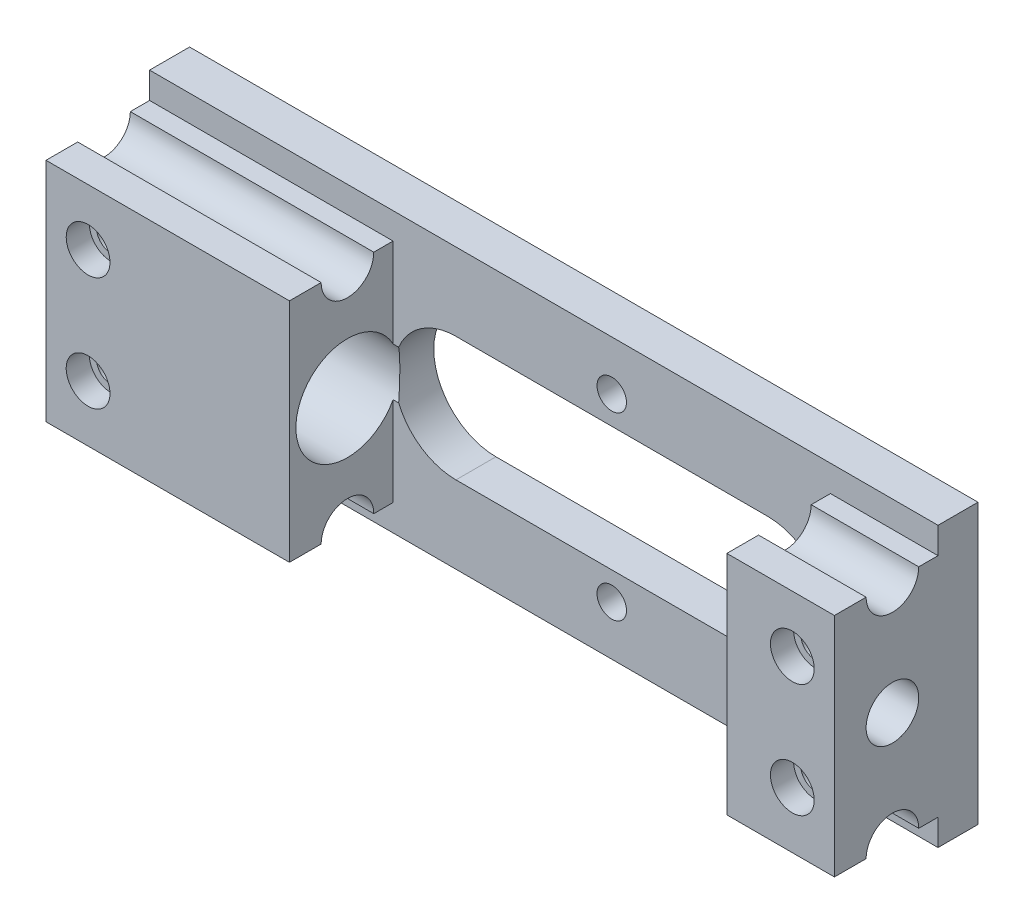
SolidWorks part; units mm, degrees
ref_plane "Front Plane" through (0, 0, 0) normal (0, 0, 1) x (1, 0, 0)
ref_plane "Top Plane" through (0, 0, 0) normal (0, 1, 0) x (1, 0, 0)
ref_plane "Right Plane" through (0, 0, 0) normal (1, 0, 0) x (0, 0, -1)
sketch "Sketch1" plane through (0, 0, 0) normal (0, 0, 1) x (1, 0, 0)
  line L1 (-22.0345, -8.4201) -> (22.0345, -8.4201)
  line L2 (-22.0345, -8.4201) -> (-22.0345, 8.4201)
  line L3 (-22.0345, 8.4201) -> (22.0345, 8.4201)
  line L4 (22.0345, -8.4201) -> (22.0345, 8.4201)
  line L5 (-22.0345, -8.4201) -> (22.0345, 8.4201) construction
  line L6 (-22.0345, 8.4201) -> (22.0345, -8.4201) construction
  point P0 (0, 0)
  dimension "D1" = 44.069
  dimension "D2" = 16.8402
extrude "Boss-Extrude1" add sketch "Sketch1" along normal blind 7.1628
sketch "Sketch2" plane through (0, 0, 7.1628) normal (0, 0, 1) x (1, 0, 0)
  line L0 (-22.0345, 0) -> (22.0345, 0) construction
  line L1 (-10.8458, 8.4201) -> (15.5448, 8.4201)
  line L2 (-10.8458, 8.4201) -> (-10.8458, -8.4201)
  line L3 (-10.8458, -8.4201) -> (15.5448, -8.4201)
  line L4 (15.5448, 8.4201) -> (15.5448, -8.4201)
  line L5 (-22.0345, 8.4201) -> (-22.0345, -8.4201) construction
  line L6 (22.0345, -8.4201) -> (22.0345, 8.4201) construction
  line L7 (-10.8458, 8.4201) -> (-22.0345, 0) construction
  line L8 (-22.0345, 0) -> (-10.8458, -8.4201) construction
  line L9 (2.3495, 8.4201) -> (2.3495, -8.4201) construction
  line L12 (22.0345, 8.4201) -> (-22.0345, 8.4201) construction
  dimension "D1" = 26.3906
  dimension "D2" = 24.384
extrude "Cut-Extrude1" cut sketch "Sketch2" against normal blind 4.75
sketch "Sketch4" plane through (0, 0, 7.1628) normal (0, 0, 1) x (1, 0, 0)
  line L0 (-10.8458, 8.4201) -> (-10.8458, -8.4201) construction
  line L1 (-22.0345, -8.4201) -> (-10.8458, -8.4201)
  line L2 (-22.0345, -8.4201) -> (-22.0345, -6.8326)
  line L3 (-22.0345, -6.8326) -> (-10.8458, -6.8326)
  line L4 (-10.8458, -8.4201) -> (-10.8458, -6.8326)
  line L5 (-22.0345, 0) -> (-10.8458, 0) construction
  line L6 (-22.0345, 8.4201) -> (-22.0345, -8.4201) construction
  line L7 (-10.8458, 8.4201) -> (-10.8458, -8.4201) construction
  line L8 (-10.8458, 8.4201) -> (-10.8458, 6.8326)
  line L9 (-22.0345, 6.8326) -> (-10.8458, 6.8326)
  line L10 (-22.0345, 8.4201) -> (-22.0345, 6.8326)
  line L11 (-22.0345, 8.4201) -> (-10.8458, 8.4201)
  line L12 (22.0345, -8.4201) -> (22.0345, 8.4201) construction
  line L13 (15.5448, -8.4201) -> (22.0345, -8.4201)
  line L14 (15.5448, -8.4201) -> (15.5448, -6.8326)
  line L15 (15.5448, -6.8326) -> (22.0345, -6.8326)
  line L16 (22.0345, -8.4201) -> (22.0345, -6.8326)
  line L17 (15.5448, 6.8326) -> (22.0345, 6.8326)
  line L18 (22.0345, 8.4201) -> (22.0345, 6.8326)
  line L19 (15.5448, 8.4201) -> (22.0345, 8.4201)
  line L20 (15.5448, 8.4201) -> (15.5448, 6.8326)
  dimension "D1" = 1.5875
extrude "Cut-Extrude9" cut sketch "Sketch4" against normal up to surface (4.75 mm away) up to face at (2.3495, 0, 2.4128)
sketch "Sketch5" plane through (-22.0345, 0, 0) normal (-1, 0, 0) x (0, 0, 1)
  line L1 (0, 0) -> (7.1628, 0) construction
  line L2 (0, 8.4201) -> (0, -8.4201) construction
  line L3 (7.1628, 6.8326) -> (7.1628, -6.8326) construction
  circle A0 centre (5.1628, -6.8326) radius 1.5875
  circle A1 centre (5.1628, 6.8326) radius 1.5875
  dimension "D1" = 3.175
  dimension "D2" = 2
extrude "Cut-Extrude10" cut sketch "Sketch5" against normal through all
sketch "Sketch14" plane through (0, 0, 7.1628) normal (0, 0, 1) x (1, 0, 0)
  line L4 (-10.8458, -6.8326) -> (-10.8458, 6.8326)
  line L5 (-10.8458, 6.8326) -> (-22.0345, 6.8326)
  line L6 (-22.0345, 6.8326) -> (-22.0345, -6.8326)
  line L7 (-22.0345, -6.8326) -> (-10.8458, -6.8326)
  line L8 (-10.8458, -6.8326) -> (-10.8458, 6.8326)
  line L9 (-10.8458, 6.8326) -> (-22.0345, 6.8326)
  line L10 (-22.0345, 6.8326) -> (-22.0345, -6.8326)
  line L11 (-22.0345, -6.8326) -> (-10.8458, -6.8326)
  line L12 (22.0345, -6.8326) -> (22.0345, 6.8326)
  line L13 (22.0345, 6.8326) -> (15.5448, 6.8326)
  line L14 (15.5448, 6.8326) -> (15.5448, -6.8326)
  line L15 (15.5448, -6.8326) -> (22.0345, -6.8326)
  line L16 (22.0345, -6.8326) -> (22.0345, 6.8326)
  line L17 (22.0345, 6.8326) -> (15.5448, 6.8326)
  line L18 (15.5448, 6.8326) -> (15.5448, -6.8326)
  line L19 (15.5448, -6.8326) -> (22.0345, -6.8326)
  dimension "D1" = 0
  dimension "D2" = 0
extrude "Boss-Extrude3" add sketch "Sketch14" along normal blind 1.5
sketch "Sketch6" plane through (0, 0, 8.6628) normal (0, 0, 1) x (1, 0, 0)
  line L0 (-22.0345, 0) -> (-10.8458, 0) construction
  line L2 (-10.8458, 6.8326) -> (-10.8458, -6.8326) construction
  line L3 (-22.0345, 6.8326) -> (-22.0345, -6.8326) construction
  circle A0 centre (-14.7955, 3.429) radius 0.889
  circle A1 centre (-14.7955, -3.429) radius 0.889
  circle A2 centre (19.4945, 3.429) radius 0.889
  circle A3 centre (19.4945, -3.429) radius 0.889
  dimension "D1" = 1.778
  dimension "D2" = 6.858
  dimension "D3" = 7.239
  dimension "D4" = 2
extrude "Cut-Extrude11" cut sketch "Sketch6" against normal through all contours A2 | A3 region at (19.4945, 3.429, 8.6628) region at (19.4945, -3.429, 8.6628)
sketch "Sketch7" plane through (0, 0, 8.6628) normal (0, 0, 1) x (1, 0, 0)
  circle A2 centre (19.4945, 3.429) radius 1.3208
  circle A3 centre (19.4945, -3.429) radius 1.3208
extrude "Cut-Extrude12" cut sketch "Sketch7" against normal blind 1.397
sketch "Sketch9" plane through (0, 0, 0) normal (0, 0, -1) x (-1, 0, 0)
  line L0 (22.0345, 8.4201) -> (22.0345, -8.4201) construction
  line L1 (-22.0345, 0) -> (22.0345, 0) construction
  line L2 (-22.0345, -8.4201) -> (-22.0345, 8.4201) construction
  circle A0 centre (-2.3495, 5.4356) radius 0.889
  circle A1 centre (-2.3495, -5.4356) radius 0.889
  dimension "D1" = 1.778
  dimension "D2" = 24.384
  dimension "D3" = 10.8712
extrude "Cut-Extrude13" cut sketch "Sketch9" against normal through all
sketch "Sketch11" plane through (0, 0, 0) normal (0, 0, -1) x (-1, 0, 0)
  line L0 (-22.0345, 0) -> (22.0345, 0) construction
  line L1 (-22.0345, -8.4201) -> (-22.0345, 8.4201) construction
  line L2 (22.0345, 8.4201) -> (22.0345, -8.4201) construction
  line L3 (-2.3495, 5.4356) -> (-2.3495, -5.4356) construction
  line L4 (-11.7495, 0) -> (7.0505, 0) construction
  line L5 (-11.7495, 3.75) -> (7.0505, 3.75)
  line L6 (-11.7495, -3.75) -> (7.0505, -3.75)
  arc A0 (-11.7495, 3.75) -> (-11.7495, -3.75) centre (-11.7495, 0) ccw
  arc A1 (7.0505, -3.75) -> (7.0505, 3.75) centre (7.0505, 0) ccw
  circle A2 centre (-2.3495, -5.4356) radius 0.889 construction
  point P12 (-2.3495, 0)
  dimension "D1" = 7.5
  dimension "D2" = 18.8
extrude "Cut-Extrude15" cut sketch "Sketch11" against normal through all
sketch "Sketch12" plane through (-10.8458, 0, 0) normal (1, 0, 0) x (0, 0, -1)
  circle A0 centre (-5.1628, 0) radius 3.1115
  dimension "D1" = 6.223
extrude "Cut-Extrude16" cut sketch "Sketch12" against normal blind 10.922 and the other way up to next
sketch "Sketch15" plane through (-22.0345, 0, 0) normal (-1, 0, 0) x (0, 0, 1)
  line L10 (8.6628, 6.8326) -> (6.7503, 6.8326)
  line L11 (3.5753, 6.8326) -> (2.4128, 6.8326)
  line L12 (2.4128, 6.8326) -> (2.4128, 8.4201)
  line L13 (2.4128, 8.4201) -> (0, 8.4201)
  line L14 (0, 8.4201) -> (0, -8.4201)
  line L15 (0, -8.4201) -> (2.4128, -8.4201)
  line L16 (2.4128, -8.4201) -> (2.4128, -6.8326)
  line L17 (2.4128, -6.8326) -> (3.5753, -6.8326)
  line L18 (6.7503, -6.8326) -> (8.6628, -6.8326)
  line L19 (8.6628, -6.8326) -> (8.6628, 6.8326)
  line L20 (8.6628, 6.8326) -> (6.7503, 6.8326)
  line L21 (3.5753, 6.8326) -> (2.4128, 6.8326)
  line L22 (2.4128, 6.8326) -> (2.4128, 8.4201)
  line L23 (2.4128, 8.4201) -> (0, 8.4201)
  line L24 (0, 8.4201) -> (0, -8.4201)
  line L25 (0, -8.4201) -> (2.4128, -8.4201)
  line L26 (2.4128, -8.4201) -> (2.4128, -6.8326)
  line L27 (2.4128, -6.8326) -> (3.5753, -6.8326)
  line L28 (6.7503, -6.8326) -> (8.6628, -6.8326)
  line L29 (8.6628, -6.8326) -> (8.6628, 6.8326)
  arc A2 (3.5753, 6.8326) -> (6.7503, 6.8326) centre (5.1628, 6.8326) ccw
  arc A3 (6.7503, -6.8326) -> (3.5753, -6.8326) centre (5.1628, -6.8326) ccw
  arc A4 (3.5753, 6.8326) -> (6.7503, 6.8326) centre (5.1628, 6.8326) ccw
  arc A5 (6.7503, -6.8326) -> (3.5753, -6.8326) centre (5.1628, -6.8326) ccw
  dimension "D1" = 0
extrude "Boss-Extrude4" add sketch "Sketch15" along normal blind 3.5
ref_plane "Plane1" through (-1.75, 0, 0) normal (1, 0, 0) x (0, 0, -1)
mirror "Mirror1" about plane through (-1.75, 0, 0) normal (1, 0, 0) of "Cut-Extrude11", "Cut-Extrude12"
sketch "Sketch16" plane through (22.0345, 0, 0) normal (1, 0, 0) x (0, 0, -1)
  circle A0 centre (-5.1628, 0) radius 1.5875
  dimension "D1" = 3.175
extrude "Cut-Extrude17" cut sketch "Sketch16" against normal up to next
